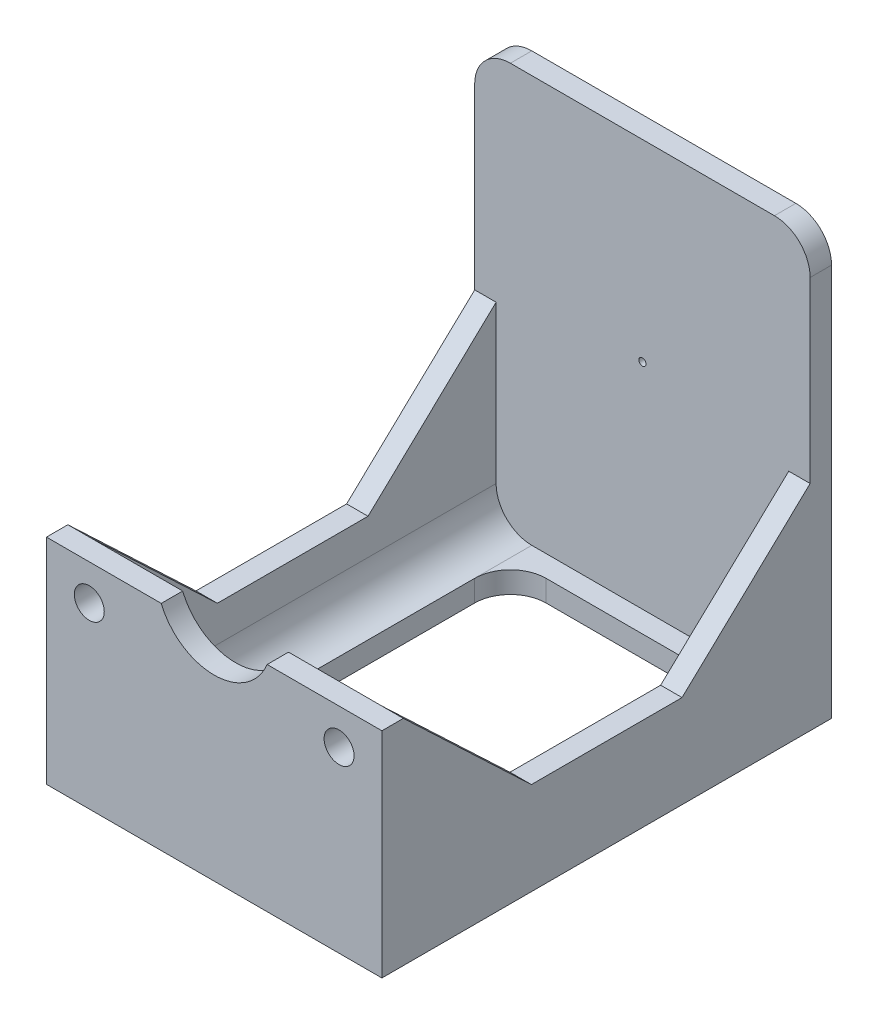
SolidWorks part; units mm, degrees
ref_plane "Front Plane" through (0, 0, 0) normal (0, 0, 1) x (1, 0, 0)
ref_plane "Top Plane" through (0, 0, 0) normal (0, 1, 0) x (1, 0, 0)
ref_plane "Right Plane" through (0, 0, 0) normal (1, 0, 0) x (0, 0, -1)
sketch "Sketch1" plane through (0, 0, 0) normal (0, 0, 1) x (1, 0, 0)
  line L0 (-17.5, 0) -> (0, 0) construction
  line L1 (0, 0) -> (0, 8) construction
  line L2 (7.4162, 5) -> (23.5, 5)
  line L3 (-23.5, -25) -> (23.5, -25)
  line L4 (-23.5, -25) -> (-23.5, 5)
  line L5 (-23.5, 5) -> (-7.4162, 5)
  line L6 (23.5, -25) -> (23.5, 5)
  line L7 (-23.5, -25) -> (23.5, 5) construction
  line L8 (-23.5, 5) -> (23.5, -25) construction
  line L9 (-7.4162, 5) -> (7.4162, 5) construction
  circle A0 centre (-17.5, 0) radius 2.1
  circle A1 centre (17.5, 0) radius 2.1
  arc A2 (-7.4162, 5) -> (7.4162, 5) centre (0, 8) ccw
  point P7 (0, -10)
  dimension "D1" = 4.2
  dimension "D3" = 6
  dimension "D4" = 5
  dimension "D5" = 8
  dimension "D2" = 35
  dimension "D6" = 8
  dimension "D7" = 30
extrude "Boss-Extrude1" add sketch "Sketch1" along normal blind 3
sketch "Sketch2" plane through (-23.5, 0, 0) normal (-1, 0, 0) x (0, 0, 1)
  line L0 (0, -25) -> (-60, -25)
  line L1 (-60, -25) -> (-60, 5)
  dimension "D1" = 60
  dimension "D2" = 30
extrude "Extrude-Thin1" add sketch "Sketch2" against normal up to surface (47 mm away) thin up to face at (23.5, -10, 1.5) thin type one direction wall 3
sketch "Sketch3" plane through (-23.5, 0, 0) normal (-1, 0, 0) x (0, 0, 1)
  line L0 (-57, 5) -> (-57, -22)
  line L1 (-57, -22) -> (0, -22)
  line L2 (0, -22) -> (0, 5)
  line L3 (0, 5) -> (-17.9444, -12)
  line L4 (-17.9444, -12) -> (-39.0556, -12)
  line L5 (-39.0556, -12) -> (-57, 5)
  line L6 (-39.0556, -12) -> (-28.5, -22) construction
  line L7 (-28.5, -22) -> (-17.9444, -12) construction
  line L8 (0, -22) -> (-57, -22) construction
  dimension "D1" = 10
extrude "Boss-Extrude2" add sketch "Sketch3" against normal blind 3 contours L5 L0 L1 L2 L3 L4
mirror "Mirror1" about plane through (0, 0, 0) normal (1, 0, 0) of "Boss-Extrude2"
sketch "Sketch4" plane through (0, -25, 0) normal (0, -1, 0) x (1, 0, 0)
  line L0 (-23.5, 3) -> (-23.5, -60) construction
  line L3 (0, -28.5) -> (0, 0) construction
  line L4 (-15.5, -54) -> (15.5, -54)
  line L7 (-15.5, -54) -> (-15.5, -3)
  line L8 (-15.5, -3) -> (15.5, -3)
  line L9 (15.5, -54) -> (15.5, -3)
  line L10 (-15.5, -54) -> (15.5, -3) construction
  line L11 (-15.5, -3) -> (15.5, -54) construction
  line L12 (23.5, -60) -> (-23.5, -60) construction
  line L13 (-23.5, 3) -> (23.5, 3) construction
  dimension "D1" = 8
  dimension "D2" = 6
  dimension "D3" = 6
extrude "Cut-Extrude1" cut sketch "Sketch4" against normal through all
fillet "Fillet3" radius 5 4 edges at (15.5, -23.5, -54) (-15.5, -23.5, -54) (15.5, -23.5, -3) (-15.5, -23.5, -3)
sketch "Sketch6" plane through (0, 5, 0) normal (0, 1, 0) x (1, 0, 0)
  line L6 (20.5, 57) -> (23.5, 57)
  line L7 (23.5, 57) -> (23.5, 60)
  line L8 (23.5, 60) -> (-23.5, 60)
  line L9 (-23.5, 60) -> (-23.5, 57)
  line L10 (-23.5, 57) -> (-20.5, 57)
  line L11 (-20.5, 57) -> (20.5, 57)
  line L12 (20.5, 57) -> (23.5, 57)
  line L13 (23.5, 57) -> (23.5, 60)
  line L14 (23.5, 60) -> (-23.5, 60)
  line L15 (-23.5, 60) -> (-23.5, 57)
  line L16 (-23.5, 57) -> (-20.5, 57)
  line L17 (-20.5, 57) -> (20.5, 57)
  dimension "D1" = 0
extrude "Boss-Extrude3" add sketch "Sketch6" along normal blind 30
sketch "Sketch7" plane through (0, -25, 0) normal (0, -1, 0) x (1, 0, 0)
  line L0 (-12.5, -8) -> (12.5, -8) construction
  line L1 (-29, -36) -> (29, -36) construction
  line L2 (-29, -36) -> (-29, -13) construction
  line L3 (-29, -13) -> (29, -13) construction
  line L4 (29, -36) -> (29, -13) construction
  line L5 (-29, -36) -> (29, -13) construction
  line L6 (-29, -13) -> (29, -36) construction
  line L7 (-23.5, 3) -> (-23.5, -60) construction
  line L8 (0, -24.5) -> (0, 0) construction
  circle A0 centre (-29, -13) radius 1.5
  circle A1 centre (-29, -36) radius 1.5
  circle A2 centre (29, -36) radius 1.5
  circle A3 centre (29, -13) radius 1.5
  point P0 (0, -24.5)
  dimension "D3" = 3
  dimension "D1" = 58
  dimension "D2" = 23
  dimension "D4" = 5
  dimension "D5" = 5.5
fillet "Fillet1" radius 5 2 edges at (20.5, -22, -28.5) (-20.5, -22, -28.5)
sketch "Sketch10" plane through (0, 0, -57) normal (0, 0, 1) x (1, 0, 0)
  circle A0 centre (0, 8) radius 0.5
  dimension "D1" = 1
extrude "Cut-Extrude3" cut sketch "Sketch10" against normal up to next
sketch "Sketch11" plane through (0, 0, -60) normal (0, 0, -1) x (-1, 0, 0)
  line L8 (18.5, -20) -> (18.5, 30)
  line L9 (18.5, 30) -> (-18.5, 30)
  line L10 (-18.5, 30) -> (-18.5, -20)
  line L11 (-18.5, -20) -> (18.5, -20)
  line L12 (18.5, -20) -> (18.5, 30) construction
  line L13 (18.5, 30) -> (-18.5, 30) construction
  line L14 (-18.5, 30) -> (-18.5, -20) construction
  line L15 (-18.5, -20) -> (18.5, -20) construction
  circle A0 centre (-18.5, 30) radius 4.15
  circle A1 centre (18.5, 30) radius 4.15
  circle A2 centre (-18.5, -20) radius 4.15
  circle A3 centre (18.5, -20) radius 4.15
  dimension "D1" = 5
  dimension "D2" = 8.3
extrude "Cut-Extrude4" cut sketch "Sketch11" against normal blind 1
fillet "Fillet2" radius 5 2 edges at (-23.5, 35, -58.5) (23.5, 35, -58.5)
